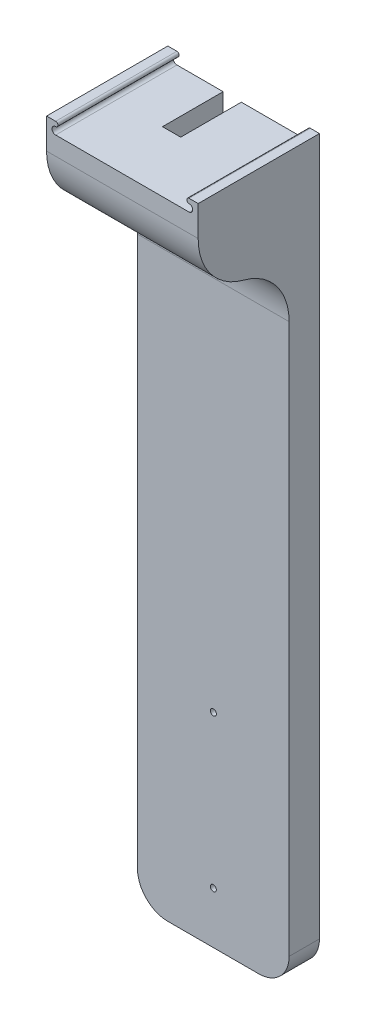
SolidWorks part; units mm, degrees
ref_plane "Přední rovina" through (0, 0, 0) normal (0, 0, 1) x (1, 0, 0)
ref_plane "Horní rovina" through (0, 0, 0) normal (0, 1, 0) x (1, 0, 0)
ref_plane "Pravá rovina" through (0, 0, 0) normal (1, 0, 0) x (0, 0, -1)
sketch "Skica1" plane through (0, 0, 0) normal (0, 0, 1) x (1, 0, 0)
  line L1 (0, 0) -> (25, 0)
  line L2 (0, 0) -> (0, 120)
  line L3 (0, 120) -> (25, 120)
  line L4 (25, 0) -> (25, 120)
  dimension "D1" = 120
  dimension "D2" = 25
extrude "Přidat vysunutím1" add sketch "Skica1" along normal blind 5
sketch "Skica2" plane through (0, 0, 0) normal (0, 0, -1) x (-1, 0, 0)
  line L0 (0, 120) -> (0, 0) construction
  line L1 (-25, 120) -> (0, 120)
  line L2 (-25, 120) -> (-25, 105)
  line L3 (-25, 105) -> (0, 105)
  line L4 (0, 120) -> (0, 105)
  dimension "D1" = 15
extrude "Přidat vysunutím2" add sketch "Skica2" against normal blind 20
fillet "Zaoblit5" radius 5 1 edges at (25, 0, 2.5)
fillet "Zaoblit6" radius 5 1 edges at (0, 0, 2.5)
sketch "Skica3" plane through (0, 0, 20) normal (0, 0, 1) x (1, 0, 0)
  line L0 (1.5, 118.04) -> (23.5, 118.04)
  line L1 (0, 120) -> (25, 120) construction
  line L4 (1.5, 120) -> (23.5, 120)
  line L5 (0, 105) -> (0, 120) construction
  line L6 (25, 120) -> (25, 105) construction
  arc A0 (23.5, 118.04) -> (23.5, 119.24) centre (23.5, 118.64) ccw
  arc A1 (23.5, 119.24) -> (23.5, 120) centre (23.5, 119.62) cw
  arc A2 (1.5, 118.04) -> (1.5, 119.24) centre (1.5, 118.64) cw
  arc A3 (1.5, 119.24) -> (1.5, 120) centre (1.5, 119.62) ccw
  dimension "D1" = 0.6
  dimension "D2" = 0.6
  dimension "D3" = 0.38
  dimension "D4" = 0.38
  dimension "D5" = 1.5
  dimension "D6" = 1.5
  dimension "D7" = 1.96
extrude "Odebrat vysunutím2" cut sketch "Skica3" against normal blind 20
fillet "Zaoblit7" radius 10 1 edges at (12.5, 105, 20)
fillet "Zaoblit8" radius 10 1 edges at (12.5, 105, 5)
sketch "Skica4" plane through (0, 118.04, 0) normal (0, 1, 0) x (1, 0, 0)
  line L0 (1.5, 0) -> (23.5, 0) construction
  line L1 (9.12, 0) -> (12.12, 0)
  line L2 (9.12, 0) -> (9.12, -10)
  line L3 (9.12, -10) -> (12.12, -10)
  line L4 (12.12, 0) -> (12.12, -10)
  line L5 (23.12, 0) -> (23.12, -20) construction
  dimension "D1" = 0
  dimension "D2" = 10
  dimension "D3" = 3
  dimension "D4" = 11
extrude "Odebrat vysunutím3" cut sketch "Skica4" against normal blind 3
sketch "Skica5" plane through (0, 0, 0) normal (0, 0, 1) x (1, 0, 0)
  line L0 (9, 21) -> (16, 21)
  line L1 (16, 21) -> (14, 43)
  line L3 (11, 43) -> (9, 21)
  line L4 (11, 43) -> (14, 43)
  line L5 (9, 21) -> (10.5, 5)
  line L6 (10.5, 5) -> (14.5, 5)
  line L7 (14.5, 5) -> (16, 21)
  line L9 (5, 0) -> (20, 0) construction
  line L10 (5.5, 24) -> (19.5, 24)
  line L11 (5.5, 24) -> (5.5, 20)
  line L12 (5.5, 20) -> (19.5, 20)
  line L13 (19.5, 24) -> (19.5, 20)
  arc A0 (5.5, 24) -> (5.5, 20) centre (5.5, 22) ccw
  arc A1 (19.5, 24) -> (19.5, 20) centre (19.5, 22) cw
  point P2 (12.5, 43)
  point P5 (12.5, 21)
  point P6 (12.5, 5)
  point P11 (12.5, 0)
  point P16 (12.5, 24)
  dimension "D1" = 7
  dimension "D2" = 3
  dimension "D3" = 22
  dimension "D4" = 16
  dimension "D5" = 5
  dimension "D6" = 4
  dimension "D7" = 19
  dimension "D8" = 14
  dimension "D9" = 4
extrude "Odebrat vysunutím4" cut sketch "Skica5" along normal blind 2 contours L3 L10 L1 L4 | L11 A0 | L11 L12 L5 L3 L10 | L10 L3 L0 L1 | L5 L12 L7 L0 | L13 L10 L1 L7 L12 | A1 L13 | L12 L5 L6 L7 region at (12.5, 22.4797, 0) region at (7.3079, 22.0229, 0) region at (12.5, 20.5023, 0) region at (17.6921, 22.0229, 0) region at (12.5, 32.3429, 0) region at (12.5, 13.1503, 0) region at (4.6512, 22, 0) region at (20.3488, 22, 0)
sketch "Skica7" plane through (0, 0, 2) normal (0, 0, -1) x (-1, 0, 0)
  line L0 (-11, 43) -> (-14, 43) construction
  line L3 (-10.5, 5) -> (-14.5, 5) construction
  circle A0 centre (-12.5, 33.6) radius 0.5
  circle A1 centre (-12.5, 8.5) radius 0.5
  point P4 (-26.1908, -0.1473)
  point P5 (-26.1908, -0.1473)
  point P6 (0, 0)
  point P9 (-12.5, 43)
  dimension "D1" = 1
  dimension "D2" = 1
  dimension "D4" = 3.5
  dimension "D3" = 25.1
extrude "Odebrat vysunutím5" cut sketch "Skica7" along normal offset from surface (2.8 mm away) 0.2 from surface up to face at (12.5, 22.6667, 2) starting at face at (12.5, 33.1998, 5)
fillet "Zaoblit9" radius 2 8 edges at (10.5, 5, 1) (14.5, 5, 1) (9.0938, 20, 1) (11, 43, 1) (14, 43, 1) (9.2727, 24, 1) (15.7273, 24, 1) (15.9062, 20, 1)
